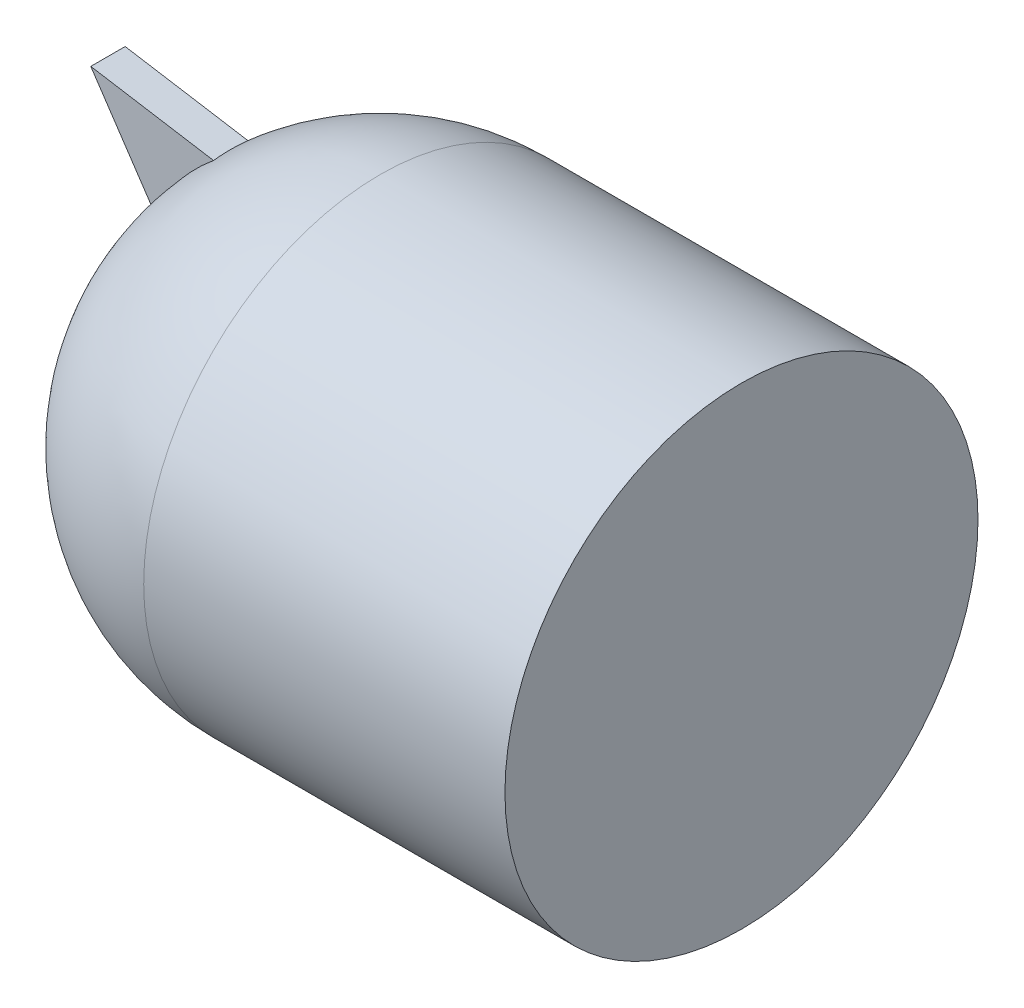
SolidWorks part; units mm, degrees
ref_plane "正面" through (0, 0, 0) normal (0, 0, 1) x (1, 0, 0)
ref_plane "平面" through (0, 0, 0) normal (0, 1, 0) x (1, 0, 0)
ref_plane "右側面" through (0, 0, 0) normal (1, 0, 0) x (0, 0, -1)
sketch "ｽｹｯﾁ2" plane through (0, 0, 0) normal (0, 0, 1) x (1, 0, 0)
  line L0 (0, 0) -> (-200, 0) construction
  line L1 (-200, 127.5) -> (0, 127.5)
  line L2 (0, 127.5) -> (0, 0)
  line L3 (-200, 0) -> (-327.5, 0) construction
  arc A0 (-200, 127.5) -> (-327.5, 0) centre (-200, 0) ccw
  dimension "D1" = 127.5
  dimension "D2" = 200
revolve "回転-薄板1" add sketch "ｽｹｯﾁ2" angle 360 about L0 wall 10
sketch "ｽｹｯﾁ3" plane through (0, 0, 0) normal (0, 0, 1) x (1, 0, 0)
  line L0 (-337.5, 0) -> (10, 0) construction
  line L1 (10, -137.5) -> (10, 137.5) construction
  line L2 (-337.5, 0) -> (-200, 137.5) construction
  line L3 (-200, 137.5) -> (-200, -137.5) construction
  line L4 (-302.6027, 34.8973) -> (-358.273, 117.7797)
  line L5 (-358.273, 117.7797) -> (-239.2322, 98.2678)
  line L6 (-239.2322, 98.2678) -> (-302.6027, 34.8973)
  line L7 (-358.273, -117.7797) -> (-239.2322, -98.2678)
  line L8 (-239.2322, -98.2678) -> (-302.6027, -34.8973)
  line L9 (-302.6027, -34.8973) -> (-358.273, -117.7797)
  arc A0 (-200, 137.5) -> (-200, -137.5) centre (-200, 0) ccw construction
extrude "ﾎﾞｽ - 押し出し1" add sketch "ｽｹｯﾁ3" along normal blind 10 and the other way blind 10
